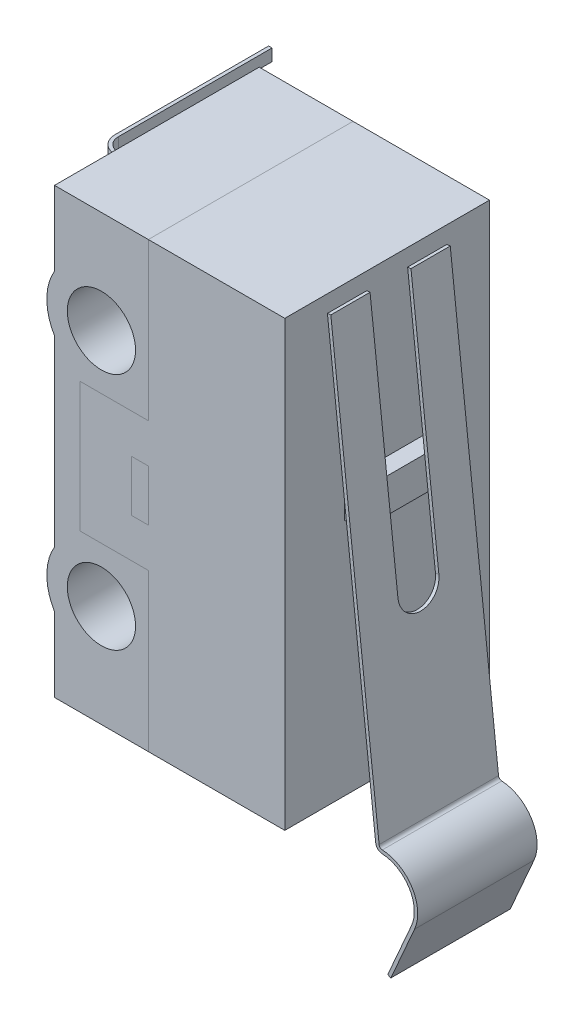
SolidWorks part; units mm, degrees
material "PUR"
ref_plane "Plan de face" through (0, 0, 0) normal (0, 0, 1) x (1, 0, 0)
ref_plane "Plan de dessus" through (0, 0, 0) normal (0, 1, 0) x (1, 0, 0)
ref_plane "Plan de droite" through (0, 0, 0) normal (1, 0, 0) x (0, 0, -1)
sketch "Esquisse1" plane through (0, 0, 0) normal (0, 0, 1) x (1, 0, 0)
  line L0 (-4, -1.9) -> (-4, -6.5)
  line L1 (-4, 6.5) -> (0, 6.5)
  line L2 (-4, 6.5) -> (-4, 1.9)
  line L3 (-4, -6.5) -> (0, -6.5)
  line L4 (0, 6.5) -> (0, -6.5)
  line L5 (-6, 1.9) -> (-4, 1.9)
  line L6 (-6, 1.9) -> (-6, -1.9)
  line L7 (-6, -1.9) -> (-4, -1.9)
  line L8 (-4, 0.75) -> (-4, -0.75)
  line L9 (-4, 0.75) -> (-4.5, 0.75)
  line L11 (-4, -0.75) -> (-4.5, -0.75)
  line L12 (-4.5, 0.75) -> (-4.5, -0.75)
  dimension "D1" = 13
  dimension "D2" = 4
  dimension "D3" = 3.8
  dimension "D4" = 1.9
  dimension "D5" = 2
  dimension "D6" = 0.5
  dimension "D7" = 1.5
  dimension "D8" = 0.75
extrude "Boss.-Extru.1" add sketch "Esquisse1" along normal mid plane 6
sketch "Esquisse2" plane through (0, 0, 3) normal (0, 0, 1) x (1, 0, 0)
  line L0 (-4, 6.5) -> (-6.75, 6.5)
  line L1 (-6.75, 6.5) -> (-6.75, 4.3182)
  line L2 (-6.75, -6.5) -> (-4, -6.5)
  line L3 (-4, -6.5) -> (0, -6.5) construction
  line L4 (-4, -6.5) -> (-4, -1.9)
  line L5 (-4, -1.9) -> (-6, -1.9)
  line L6 (-6, -1.9) -> (-6, 1.9)
  line L7 (-6, 1.9) -> (-4, 1.9)
  line L8 (-4, 1.9) -> (-4, 6.5)
  line L9 (-4, 0.75) -> (-4, -0.75)
  line L10 (-4, -0.75) -> (-4.5, -0.75)
  line L11 (-4.5, -0.75) -> (-4.5, 0.75)
  line L12 (-4.5, 0.75) -> (-4.5, -0.75) construction
  line L13 (-4, 0.75) -> (-4.5, 0.75) construction
  line L14 (-4.5, 0.75) -> (-4, 0.75)
  line L15 (0, 0) -> (-15.7696, 0) construction
  line L16 (-5.375, 6.5) -> (-5.375, 0) construction
  line L17 (-6.75, 2.6818) -> (-6.75, -2.6818)
  line L18 (-6.75, -4.3182) -> (-6.75, -6.5)
  circle A0 centre (-5.375, 3.5) radius 1
  arc A1 (-6.75, 4.3182) -> (-6.75, 2.6818) centre (-5.375, 3.5) ccw
  circle A2 centre (-5.375, -3.5) radius 1
  arc A3 (-6.75, -4.3182) -> (-6.75, -2.6818) centre (-5.375, -3.5) cw
  dimension "D1" = 2.75
  dimension "D2" = 2
  dimension "D4" = 3.2
  dimension "D3" = 3
extrude "Boss.-Extru.2" add sketch "Esquisse2" against normal up to surface (6 mm away) separate body up to face at (-3.5, 0, -3)
sketch "Esquisse3" plane through (0, 0, 0) normal (0, 0, 1) x (1, 0, 0)
  line L0 (0, -6.5) -> (0, 6.5) construction
  line L1 (0, 1.5) -> (0.5, 1.5)
  line L2 (0, 1.5) -> (0, 0.5)
  line L3 (0, 0.5) -> (0.5, 0.5)
  line L4 (0.5, 1.5) -> (0.5, 0.5)
  line L5 (0, 6.5) -> (-4, 6.5) construction
  dimension "D1" = 5
  dimension "D2" = 1
  dimension "D3" = 0.5
extrude "Boss.-Extru.3" add sketch "Esquisse3" along normal mid plane 2.5 separate body
sketch "Esquisse4" plane through (0, 0, 0) normal (0, 0, 1) x (1, 0, 0)
  line L0 (0, 6) -> (1.4154, -6.7384)
  line L1 (0, -6.5) -> (0, 6.5) construction
  line L2 (1.4356, -6.9205) -> (1.745, -9.705) construction
  line L3 (1.7669, -9.9021) -> (2.462, -8.3157)
  line L4 (0.0994, 6.011) -> (1.5148, -6.7274)
  line L5 (1.8585, -9.9423) -> (2.5536, -8.3558)
  line L6 (1.7669, -9.9021) -> (1.8585, -9.9423)
  line L7 (0.0994, 6.011) -> (0, 6)
  arc A0 (2.462, -8.3157) -> (1.6028, -6.916) centre (1.546, -7.9144) ccw
  arc A1 (1.4154, -6.7384) -> (1.6028, -6.916) centre (1.6142, -6.7163) ccw
  arc A2 (1.5148, -6.7274) -> (1.6085, -6.8161) centre (1.6142, -6.7163) ccw
  arc A3 (2.5536, -8.3558) -> (1.6085, -6.8161) centre (1.546, -7.9144) ccw
  dimension "D3" = 2
  dimension "D5" = 0.2
  dimension "D1" = 0.5
  dimension "D2" = 13
  dimension "D4" = 3
  dimension "D6" = 0.1
extrude "Boss.-Extru.4" add sketch "Esquisse4" along normal mid plane 3.5 separate body
sketch "Esquisse5" plane through (0.7579, 0.0842, 0) normal (0.9939, 0.1104, 0) x (0, 0, -1)
  line L0 (0, 5.9633) -> (0, -6.6663) construction
  line L1 (-1.75, 5.9633) -> (1.75, 5.9633) construction
  line L2 (-0.6, 5.9633) -> (-0.6, -1.4367)
  line L3 (-0.6, 5.9633) -> (0.6, 5.9633)
  line L4 (0.6, 5.9633) -> (0.6, -1.4367)
  arc A0 (-0.6, -1.4367) -> (0.6, -1.4367) centre (0, -1.4367) ccw
  dimension "D2" = 1.2
  dimension "D1" = 0.6
extrude "Enlèv. mat.-Extru.1" cut sketch "Esquisse5" against normal blind 0.1
sketch "Esquisse6" plane through (0, 0, 0) normal (0, 1, 0) x (1, 0, 0)
  line L0 (-6.975, 0) -> (-7.975, 0)
  line L1 (-6.975, 3) -> (-6.975, -3) construction
  line L2 (-8.475, 0.5) -> (-8.475, 5)
  line L3 (-6.75, 3) -> (-4, 3) construction
  line L4 (-6.975, 0.1) -> (-7.975, 0.1)
  line L5 (-8.375, 0.5) -> (-8.375, 5)
  line L6 (-8.475, 5) -> (-8.375, 5)
  line L7 (-6.975, 0.1) -> (-6.75, 0.1)
  line L8 (-6.75, 3) -> (-6.75, -3) construction
  line L9 (-6.75, 0.1) -> (-6.75, 0)
  line L10 (-6.75, 0) -> (-6.975, 0)
  arc A0 (-7.975, 0) -> (-8.475, 0.5) centre (-7.975, 0.5) cw
  arc A1 (-7.975, 0.1) -> (-8.375, 0.5) centre (-7.975, 0.5) cw
  dimension "D3" = 0.5
  dimension "D1" = 1.5
  dimension "D2" = 2
  dimension "D4" = 0.1
extrude "Boss.-Extru.5" add sketch "Esquisse6" along normal mid plane 0.35 separate body
pattern_linear "Répétition linéaire1" count 2 spacing 5 along (0, -1, 0) count 2 spacing 5 along (0, 1, 0) of "Boss.-Extru.5"
equation "\"D4@Esquisse1\"=\"D3@Esquisse1\"/2"
equation "\"D8@Esquisse1\"=\"D7@Esquisse1\"/2"
